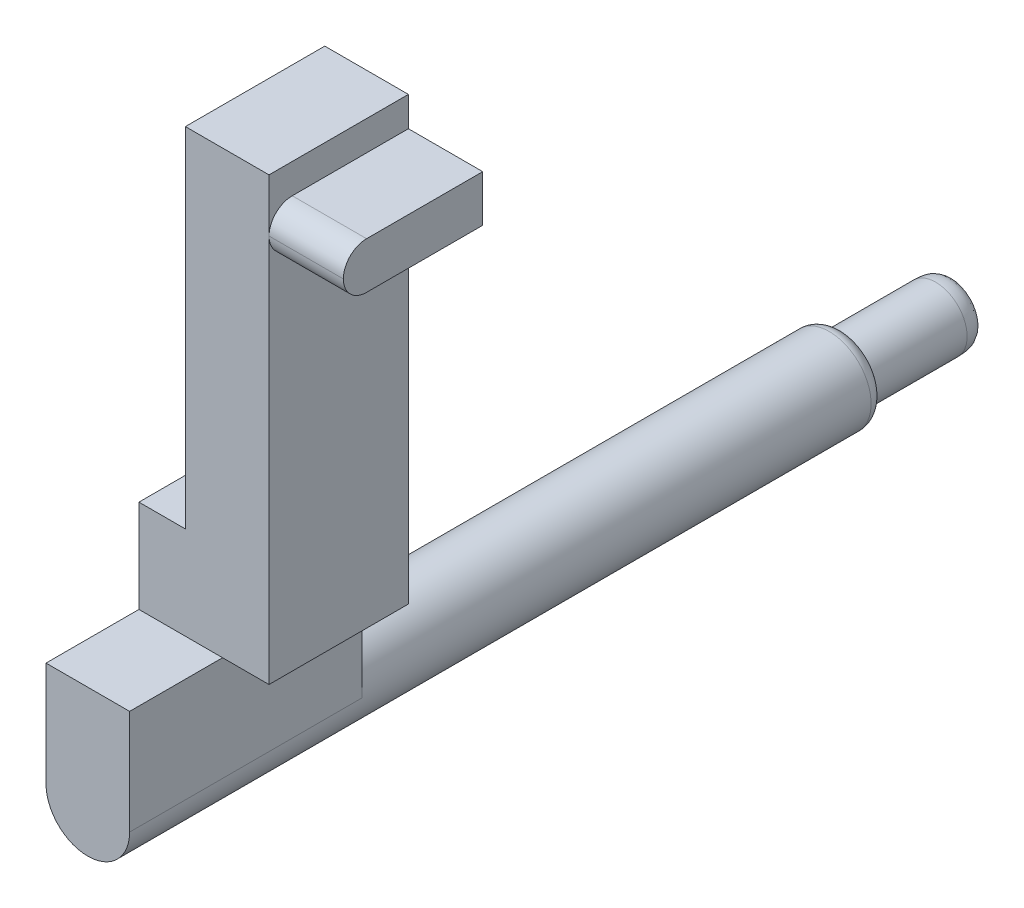
SolidWorks part; units mm, degrees
material "ABS"
ref_plane "Alzado" through (0, 0, 0) normal (0, 0, 1) x (1, 0, 0)
ref_plane "Planta" through (0, 0, 0) normal (0, 1, 0) x (1, 0, 0)
ref_plane "Vista lateral" through (0, 0, 0) normal (1, 0, 0) x (0, 0, -1)
sketch "Croquis1" plane through (0, 0, 0) normal (0, 0, 1) x (1, 0, 0)
  circle A4 centre (-6.3971, 9.5757) radius 0.675
  dimension "D1" = 1.35
extrude "Saliente-Extruir1" add sketch "Croquis1" against normal blind 2.4
fillet "Redondeo1" radius 0.4 1 edges at (-5.7221, 9.5757, -2.4) conic radius 0.2
sketch "Croquis2" plane through (0, 0, 0) normal (0, 0, 1) x (1, 0, 0)
  circle A5 centre (-6.3971, 9.5757) radius 0.9
  dimension "D1" = 1.8
extrude "Saliente-Extruir2" add sketch "Croquis2" along normal blind 12.25
sketch "Croquis3" plane through (0, 0, 12.25) normal (0, 0, 1) x (1, 0, 0)
  line L0 (-7.2971, 9.5757) -> (-5.4971, 9.5757)
  circle A0 centre (-6.3971, 9.5757) radius 0.9
  circle A1 centre (-6.3971, 9.5757) radius 0.9 construction
  circle M2 centre (-6.3971, 9.5757) radius 0.9
  dimension "D1" = 1.8
extrude "Saliente-Extruir3" add sketch "Croquis3" along normal blind 2 contours L0 M2 region at (-6.3971, 9.1937, 12.25)
sketch "Croquis4" plane through (0, 9.5757, 0) normal (0, 1, 0) x (1, 0, 0)
  line L0 (-6.3971, -10.25) -> (-6.3971, -13.25) construction
  line L1 (-7.2971, -14.25) -> (-5.4971, -14.25) construction
  line L3 (-5.4971, -13.25) -> (-7.2971, -13.25) construction
  line L4 (-5.4971, -14.25) -> (-5.4971, -12.25) construction
  line L5 (-7.2971, -12.25) -> (-7.2971, -14.25)
  line L6 (-7.2971, -14.25) -> (-5.4971, -14.25)
  line L9 (-7.2971, -12.25) -> (-5.4971, -12.25)
  line L10 (-5.4971, -14.25) -> (-5.4971, -12.25)
  line L11 (-7.2971, -12.25) -> (-5.4971, -12.25) construction
  line M8 (-5.4971, -12.25) -> (-7.2971, -12.25)
  line M9 (-7.2971, -12.25) -> (-7.2971, -14.25)
  line M11 (-5.4971, -14.25) -> (-5.4971, -12.25)
extrude "Saliente-Extruir4" add sketch "Croquis4" along normal blind 4.25 contours L9 L5 M9 | L10 L9 M11 | M11 M8 M9 | L6 M11 M9 | L6 M9 | L6 M11 | L6 M9 | L6 M9 M11 | L6 M11 region at (-6.3971, 9.5757, 13.25)
sketch "Croquis6" plane through (-5.4971, 0, 0) normal (-1, 0, 0) x (0, 0, 1)
  line L0 (14.25, 13.8257) -> (14.25, 9.5757) construction
  line L1 (14.25, 13.8257) -> (12.25, 13.8257)
  line L2 (14.25, 13.8257) -> (14.25, 11.8257)
  line L3 (14.25, 11.8257) -> (12.25, 11.8257)
  line L4 (12.25, 13.8257) -> (12.25, 11.8257)
  line L5 (12.25, 13.8257) -> (12.25, 9.5757) construction
  line L7 (12.25, 13.8257) -> (14.25, 13.8257) construction
  dimension "D1" = 2
extrude "Saliente-Extruir5" add sketch "Croquis6" against normal blind 1
sketch "Croquis7" plane through (0, 13.8257, 0) normal (0, 1, 0) x (1, 0, 0)
  line L1 (-6.2971, -12.25) -> (-4.4971, -12.25)
  line L2 (-4.4971, -14.25) -> (-7.2971, -14.25) construction
  line L5 (-6.2971, -12.25) -> (-6.2971, -14.25)
  line L7 (-6.2971, -14.25) -> (-6.2971, -12.25)
  line L12 (-6.2971, -12.25) -> (-4.4971, -12.25)
  line L13 (-4.4971, -14.25) -> (-4.4971, -12.25)
  line L14 (-6.2971, -14.25) -> (-4.4971, -14.25)
  line L15 (-4.4971, -12.25) -> (-4.4971, -14.25)
  line M26 (-7.2971, -14.25) -> (-4.4971, -14.25)
  line M27 (-4.4971, -14.25) -> (-4.4971, -12.25)
  line M33 (-4.4971, -12.25) -> (-7.2971, -12.25)
  dimension "D1" = 1.8
extrude "Saliente-Extruir6" add sketch "Croquis7" along normal blind 7.5 contours L5 M33 M26 M27 region at (-5.3971, 13.8257, 13.25)
sketch "Croquis9" plane through (0, 0, 12.25) normal (0, 0, -1) x (-1, 0, 0)
  line L0 (4.4971, 21.3257) -> (4.4971, 11.8257) construction
  line L2 (4.4971, 21.3257) -> (6.2971, 21.3257) construction
  line L4 (2.8971, 20.6857) -> (4.4971, 20.6857)
  line L5 (2.8971, 20.6857) -> (2.8971, 19.6857)
  line L6 (2.8971, 19.6857) -> (4.4971, 19.6857)
  line L7 (4.4971, 20.6857) -> (4.4971, 19.6857)
  line L11 (4.4971, 20.6857) -> (4.4971, 19.6857) construction
  dimension "D1" = 0.64
  dimension "D2" = 1
  dimension "D3" = 1.6
extrude "Saliente-Extruir7" add sketch "Croquis9" against normal blind 2
fillet "Redondeo2" radius 0.5 2 edges at (-3.6971, 20.6857, 14.25) (-3.6971, 19.6857, 14.25) first distance on face at (-5.2804, 16.3915, 14.25)
sketch "Croquis10" plane through (0, 0, 12.25) normal (0, 0, -1) x (-1, 0, 0)
  line L56 (4.4971, 19.6857) -> (2.8971, 19.6857)
  line L66 (2.8971, 20.6857) -> (2.8971, 19.6857)
  line L67 (4.4971, 20.6857) -> (2.8971, 20.6857)
  line L68 (4.4971, 21.3257) -> (4.4971, 20.6857)
  line L69 (6.2971, 21.3257) -> (4.4971, 21.3257)
  line L70 (6.2971, 13.8257) -> (6.2971, 21.3257)
  line L71 (7.2971, 13.8257) -> (6.2971, 13.8257)
  line L72 (4.4971, 19.6857) -> (4.4971, 11.8257)
  line L73 (4.4971, 11.8257) -> (5.4971, 11.8257)
  line L74 (5.4971, 11.8257) -> (5.4971, 9.5757)
  line L75 (7.2971, 9.5757) -> (7.2971, 13.8257)
  line L76 (2.8971, 20.6857) -> (2.8971, 19.6857)
  line L77 (4.4971, 20.6857) -> (2.8971, 20.6857)
  line L78 (4.4971, 21.3257) -> (4.4971, 20.6857)
  line L79 (6.2971, 21.3257) -> (4.4971, 21.3257)
  line L80 (6.2971, 13.8257) -> (6.2971, 21.3257)
  line L81 (7.2971, 13.8257) -> (6.2971, 13.8257)
  line L82 (4.4971, 19.6857) -> (4.4971, 11.8257)
  line L83 (4.4971, 11.8257) -> (5.4971, 11.8257)
  line L84 (5.4971, 11.8257) -> (5.4971, 9.5757)
  line L85 (7.2971, 9.5757) -> (7.2971, 13.8257)
  arc A11 (7.2971, 9.5757) -> (5.4971, 9.5757) centre (6.3971, 9.5757) ccw
  arc A12 (7.2971, 9.5757) -> (5.4971, 9.5757) centre (6.3971, 9.5757) ccw
  dimension "D1" = 0
extrude "Saliente-Extruir8" add sketch "Croquis10" along normal blind 1
sketch "Croquis12" plane through (0, 0, 14.25) normal (0, 0, 1) x (1, 0, 0)
  line L1 (-5.4971, 11.8257) -> (-7.2971, 11.8257)
  line L2 (-5.4971, 11.8257) -> (-5.4971, 9.5757)
  line L4 (-7.2971, 11.8257) -> (-7.2971, 9.5757)
  arc A0 (-7.2971, 9.5757) -> (-5.4971, 9.5757) centre (-6.3971, 9.5757) ccw
extrude "Saliente-Extruir9" add sketch "Croquis12" along normal blind 2
fillet "Redondeo3" radius 0.3 1 edges at (-5.4971, 9.5757, 0)
